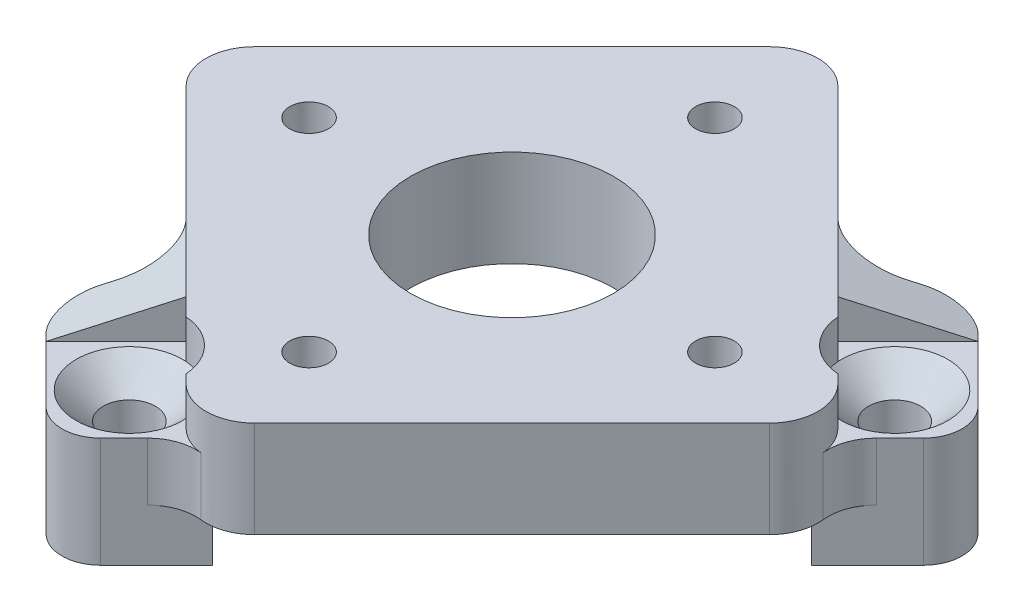
SolidWorks part; units mm, degrees
other "Markup1"
sketch "Sketch13" plane through (18.3326, 5, 18.3326) normal (0.1488, 0.9786, 0.1422) x (0.9219, -0.0853, -0.378)
ref_plane "Front Plane" through (0, 0, 0) normal (0, 0, 1) x (1, 0, 0)
ref_plane "Top Plane" through (0, 0, 0) normal (0, 1, 0) x (1, 0, 0)
ref_plane "Right Plane" through (0, 0, 0) normal (1, 0, 0) x (0, 0, -1)
sketch "Sketch1" plane through (0, 0, 0) normal (0, 1, 0) x (1, 0, 0)
  line L0 (0, 10.5) -> (0, -10.5) construction
  line L1 (10.5, 0) -> (-10.5, 0) construction
  line L2 (0, 10.5) -> (10.5, 0) construction
  line L3 (10.5, 0) -> (0, -10.5) construction
  line L4 (0, -10.5) -> (-10.5, 0) construction
  line L8 (-10.5, 0) -> (0, 10.5) construction
  line L9 (1.7678, 15.0962) -> (15.0962, 1.7678)
  line L10 (15.0962, -1.7678) -> (1.7678, -15.0962)
  line L11 (-1.7678, -15.0962) -> (-15.0962, -1.7678)
  line L12 (-15.0962, 1.7678) -> (-1.7678, 15.0962)
  line L13 (16.864, 0) -> (0, -16.864) construction
  line L14 (0, -16.864) -> (-16.864, 0) construction
  line L15 (0, 16.864) -> (16.864, 0) construction
  line L16 (-16.864, 0) -> (0, 16.864) construction
  circle A7 centre (0, 10.5) radius 0.5
  circle A8 centre (0, -10.5) radius 0.5
  circle A9 centre (10.5, 0) radius 0.5
  circle A10 centre (-10.5, 0) radius 0.5
  circle A11 centre (0, 0) radius 5.25
  arc A12 (1.7678, -15.0962) -> (-1.7678, -15.0962) centre (0, -13.3284) cw
  arc A13 (15.0962, 1.7678) -> (15.0962, -1.7678) centre (13.3284, 0) cw
  arc A14 (-15.0962, -1.7678) -> (-15.0962, 1.7678) centre (-13.3284, 0) cw
  arc A15 (1.7678, 15.0962) -> (-1.7678, 15.0962) centre (0, 13.3284) ccw
  dimension "D2" = 1
  dimension "D3" = 10.5
  dimension "D4" = 4.5
  dimension "D5" = 2.5
  dimension "D1" = 21
extrude "Boss-Extrude1" add sketch "Sketch1" along normal blind 5
sketch "Sketch4" plane through (0, 0, 0) normal (0, -1, 0) x (1, 0, 0)
  circle A0 centre (0, 10.5) radius 3
  circle A1 centre (10.5, 0) radius 3
  circle A2 centre (-10.5, 0) radius 3
  circle A3 centre (0, -10.5) radius 3
  point P0 (0, 10.5)
  point P3 (10.5, 0)
  point P6 (-10.5, 0)
  point P9 (0, -10.5)
  dimension "D1" = 6
ref_plane "Plane1" through (0, -2.7, 0) normal (0, 1, 0) x (1, 0, 0)
ref_plane "Plane2" through (8.432, 0, 8.432) normal (0.7071, 0, 0.7071) x (0.7071, 0, -0.7071)
ref_plane "Plane3" through (2.7751, 0, 2.7751) normal (0.7071, 0, 0.7071) x (0.7071, 0, -0.7071)
sketch "Sketch3" plane through (0, -2.7, 0) normal (0, 1, 0) x (1, 0, 0)
  line L0 (-8.432, 8.432) -> (8.432, -8.432) construction
  line L1 (-1.7678, 15.0962) -> (-15.0962, 1.7678) construction
  line L2 (1.7678, -15.0962) -> (15.0962, -1.7678) construction
  line L3 (9.8995, 9.8995) -> (14.8492, 4.9497) construction
  line L5 (10.5375, 4.9497) -> (14.8492, 0.638)
  line L12 (15.0962, 1.7678) -> (1.7678, 15.0962) construction
  line L13 (14.8492, 0.638) -> (19.161, 4.9497)
  line L20 (0, 0) -> (9.8995, 9.8995) construction
  line L21 (15.0962, 1.7678) -> (1.7678, 15.0962) construction
  line L22 (19.161, 4.9497) -> (14.8492, 9.2615)
  line L23 (14.8492, 9.2615) -> (10.5375, 4.9497)
  line L24 (19.161, 4.9497) -> (10.5375, 4.9497) construction
  line L25 (-4.9497, -19.161) -> (-4.9497, -10.5375) construction
  line L26 (-9.8995, -9.8995) -> (-4.9497, -14.8492) construction
  line L27 (-9.2615, -14.8492) -> (-4.9497, -10.5375)
  line L28 (-4.9497, -19.161) -> (-9.2615, -14.8492)
  line L29 (-0.638, -14.8492) -> (-4.9497, -19.161)
  line L30 (-4.9497, -10.5375) -> (-0.638, -14.8492)
  line L31 (10.5375, 4.9497) -> (8.7697, 6.7175)
  line L32 (8.7697, 6.7175) -> (13.0815, 11.0293)
  line L33 (13.0815, 11.0293) -> (14.8492, 9.2615)
  line L34 (-4.9497, -10.5375) -> (-6.7175, -8.7697)
  line L35 (-6.7175, -8.7697) -> (-11.0293, -13.0815)
  line L36 (-11.0293, -13.0815) -> (-9.2615, -14.8492)
  circle A2 centre (14.8492, 4.9497) radius 1.3
  circle A3 centre (-4.9497, -14.8492) radius 1.3
  dimension "D1" = 2.6
  dimension "D2" = 7
  dimension "D3" = 3.0489
  dimension "D4" = 14
  dimension "D5" = 2.5
extrude "Boss-Extrude4" add sketch "Sketch3" along normal offset from surface (5.7 mm away) 3 contours L30 L27 L28 L29 A3 | L35 L36 L27 L34 | L22 L23 L5 L13 A2 | L33 L32 L31 L23 region at (12.7796, -2.7, -7.0194) region at (11.8095, -2.7, -7.9895) region at (-7.9895, -2.7, 11.8095) region at (-7.0194, -2.7, 12.7796) up to face at (-10.5, 0, 0.5)
sketch "Sketch7" plane through (2.7751, 0, 2.7751) normal (0.7071, 0, 0.7071) x (0.7071, 0, -0.7071)
  line L0 (11.9246, 5) -> (17.0489, 3)
  line L1 (-11.9246, 5) -> (-17.0489, 3)
  line L2 (-17.0489, 3) -> (-11.9246, 3)
  line L3 (-11.9246, 3) -> (-11.9246, 5)
  line L4 (11.9246, 5) -> (11.9246, 3)
  line L5 (11.9246, 3) -> (17.0489, 3)
extrude "Boss-Extrude6" add sketch "Sketch7" against normal up to surface (2.4735 mm away) up to face at (-8.3842, 0.1, 10.4364)
fillet "Fillet1" radius 2.5 4 edges at (-7.4059, 2.5, 9.4581) (9.4581, 2.5, -7.4059) (15.4816, 1.5, -1.2704) (-1.2704, 1.5, 15.4816)
fillet "Fillet2" radius 2 4 edges at (-11.0293, 0.15, 13.0815) (-4.9497, 0.15, 19.161) (13.0815, 0.15, -11.0293) (19.161, 0.15, -4.9497)
hole_wizard "Ø2.0mm Dowel Hole1" positions "Sketch4" profile "Sketch11" hole size "Ø2.0" standard "ANSI Metric"
sketch "Sketch11" plane through (0, 0, 10.5) normal (1, 0, 0) x (0, 0, -1)
  line L0 (0, 0) -> (0, 43.5309)
  line L1 (0, 43.5309) -> (1, 42.93)
  line L2 (1, 42.93) -> (1, 0)
  line L5 (1, 0) -> (0, 0)
  line L10 (0, 43.5309) -> (-1, 42.93) construction
  line L11 (0, -6.35) -> (0, 107.95) construction
  dimension "Hole Dia." = 2
  dimension "Hole Depth" = 42.93
  dimension "Drill Angle" = 118
hole_wizard "CSK for M2.5 Flat Head Machine Screw1" positions "3DSketch1" profile "Sketch12" countersink size "M2.5" standard "ANSI Metric" end condition through all
sketch3d "3DSketch1"
  line L0 (-4.9497, 3, 14.8492) -> (-4.9497, -2.7, 14.8492) construction
  line L1 (14.8492, 3, -4.9497) -> (14.8492, -2.7, -4.9497) construction
  point P0 (-4.9497, 3, 14.8492)
  point P4 (14.8492, 3, -4.9497)
sketch "Sketch12" plane through (-4.9497, 3, 14.8492) normal (1, 0, 0) x (0, 0, 1)
  line L0 (0, 0) -> (0, 5.7)
  line L1 (0, 5.7) -> (1.35, 5.7)
  line L2 (1.35, 5.7) -> (1.35, 1.4)
  line L3 (1.35, 1.4) -> (2.75, 0)
  line L5 (2.75, 0) -> (0, 0)
  line L6 (-1.35, 1.4) -> (-2.75, 0) construction
  line L11 (0, -6.35) -> (0, 107.95) construction
  dimension "Thru Hole Dia." = 2.7
  dimension "Thru Hole Depth" = 5.7
  dimension "Near C'Sink Dia." = 5.5
  dimension "Near C'Sink Angle" = 90
sketch "Sketch14" plane through (0, 3, 0) normal (0, 1, 0) x (1, 0, 0)
  circle A0 centre (-4.9497, -14.8492) radius 2.75
  circle A1 centre (14.8492, 4.9497) radius 2.75
extrude "Cut-Extrude1" cut sketch "Sketch14" along normal through all
